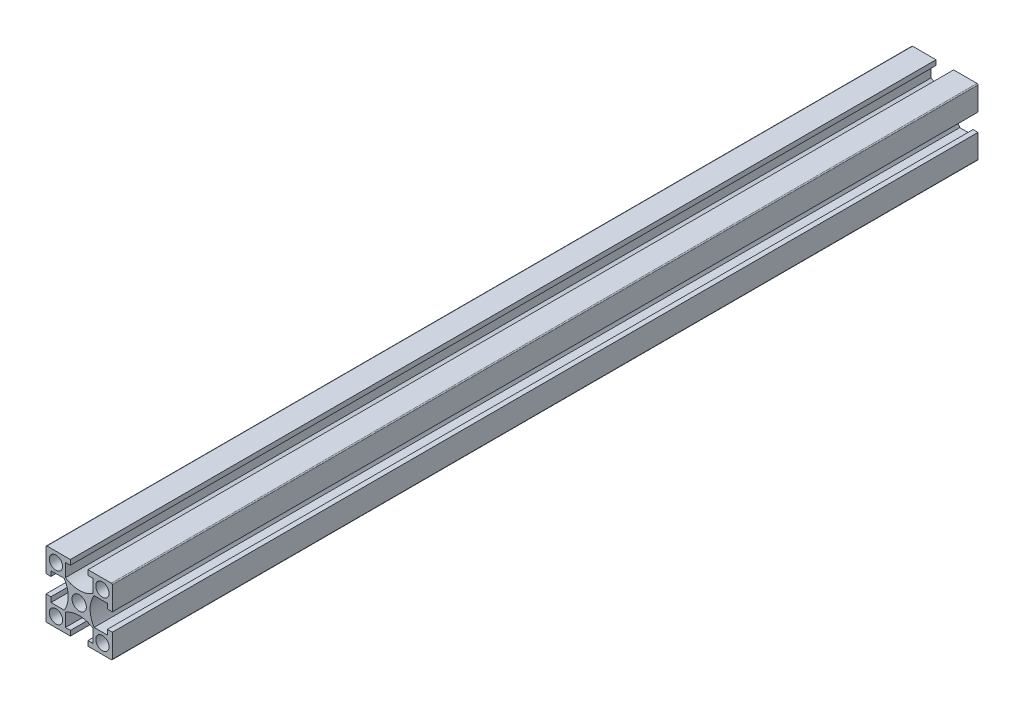
SolidWorks part; units mm, degrees
material "3.0255 (EN-AW 1350A)"
ref_plane "정면" through (0, 0, 0) normal (0, 0, 1) x (1, 0, 0)
ref_plane "윗면" through (0, 0, 0) normal (0, 1, 0) x (1, 0, 0)
ref_plane "우측면" through (0, 0, 0) normal (1, 0, 0) x (0, 0, -1)
sketch "스케치1" plane through (0, 0, 0) normal (0, 0, 1) x (1, 0, 0)
  line L0 (0, 32.0265) -> (0, -31.6588) construction
  line L1 (-10, 10) -> (-10, -10)
  line L2 (-10, 10) -> (10, 10)
  line L3 (-10, 2.65) -> (-8.5, 2.65)
  line L4 (13.6618, 0) -> (-11.6993, 0) construction
  line L5 (-8.5, 2.65) -> (-8.5, 4.15)
  line L6 (-8.5, 4.15) -> (-4.5032, 4.15)
  line L7 (-10, -2.65) -> (-8.5, -2.65)
  line L8 (-8.5, -2.65) -> (-8.5, -4.15)
  line L9 (-8.5, -4.15) -> (-4.5032, -4.15)
  line L10 (-10, -10) -> (10, -10)
  line L11 (10, 10) -> (10, -10)
  circle A0 centre (-7, 7) radius 2
  circle A1 centre (-7, -7) radius 2
  arc A2 (-4.5032, 4.15) -> (-4.5032, -4.15) centre (-11.0587, 0) cw
  circle A3 centre (0, 0) radius 2.15
  circle A4 centre (7, 7) radius 2
  circle A5 centre (7, -7) radius 2
  point P21 (-10, 0)
  point P23 (-3.3, 0)
  point P31 (0, -10)
  point P32 (0, 10)
  dimension "D3" = 4
  dimension "D9" = 6.7
  dimension "D10" = 4.3
  dimension "D11" = 7.7587
  dimension "D1" = 20
  dimension "D2" = 20
  dimension "D4" = 14
  dimension "D5" = 14
  dimension "D6" = 5.3
  dimension "D7" = 8.3
  dimension "D8" = 1.5
extrude "보스-돌출1" add sketch "스케치1" along normal blind 261 contours A0 | A4 | A3 | A5 | A1 | A2 L6 L5 L3 L1 L7 L8 L9 | L2 L11 L10 L1 region at (-6.6069, 0, 0) region at (-7, 7, 0) region at (-7, -7, 0) region at (0, 0, 0) region at (7, 7, 0) region at (7, -7, 0)
extrude "컷-돌출1" cut sketch "스케치1<3>" along normal up to next contours A2 L6 L5 L3 L1 L7 L8 L9 region at (-6.6069, 0, 0)
sketch "스케치1<3>" plane through (0, 0, 0) normal (0, 0, 1) x (1, 0, 0) same geometry as "스케치1"
pattern_circular "원형 패턴1" count 4 over 360 about axis through (0, 0, 261) along (0, 0, -1) of "컷-돌출1" reverse direction yes
fillet "필렛1" radius 0.3 4 edges at (10, -10, 130.5) (-10, -10, 130.5) (-10, 10, 130.5) (10, 10, 130.5)
sketch "스케치3" plane through (0, 10, 0) normal (0, 1, 0) x (1, 0, 0)
  line L0 (-4.15, -261) -> (4.15, -261) construction
  circle A0 centre (0, -11) radius 2.5
  circle A1 centre (0, -250) radius 2.5
  dimension "D1" = 11
  dimension "D2" = 11
extrude "컷-돌출2" cut sketch "스케치3" against normal through all
sketch "스케치4" plane through (0, 10, 0) normal (0, 1, 0) x (1, 0, 0)
  line L0 (-4.15, -261) -> (4.15, -261) construction
  circle A1 centre (0, -108) radius 2.15
  circle A2 centre (0, -56) radius 2.15
  dimension "D1" = 153
  dimension "D2" = 52
extrude "컷-돌출3" cut sketch "스케치4" against normal through all
